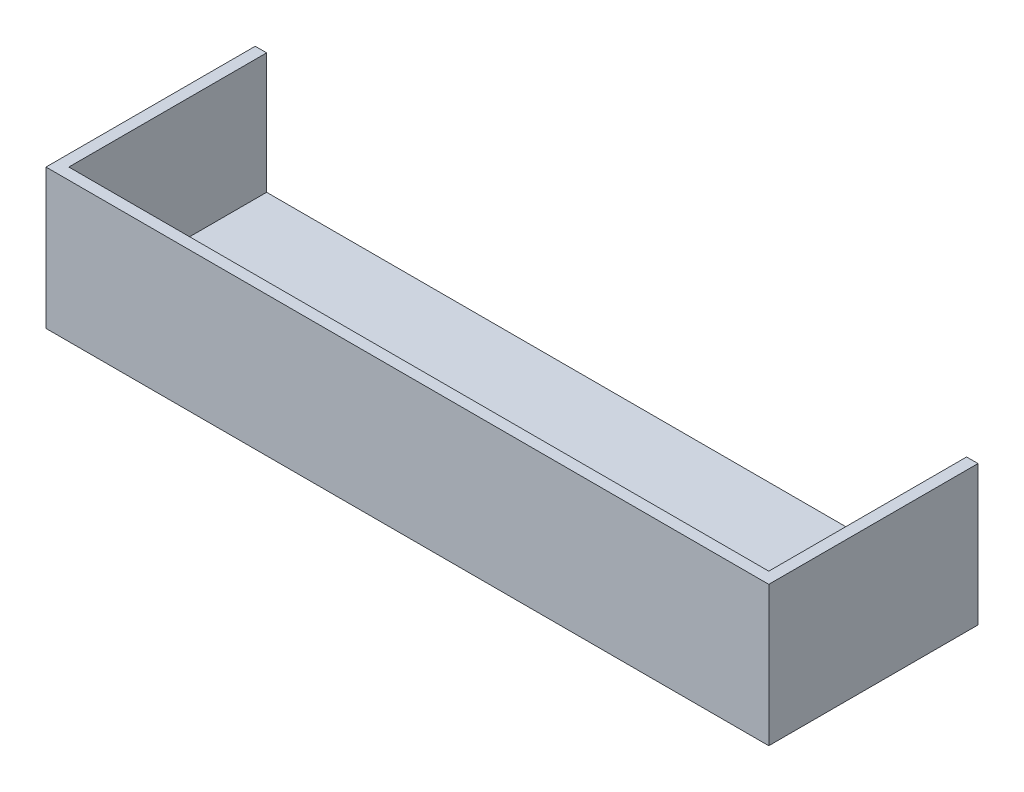
SolidWorks part; units mm, degrees
ref_plane "Front Plane" through (0, 0, 0) normal (0, 0, 1) x (1, 0, 0)
ref_plane "Top Plane" through (0, 0, 0) normal (0, 1, 0) x (1, 0, 0)
ref_plane "Right Plane" through (0, 0, 0) normal (1, 0, 0) x (0, 0, -1)
sketch "Sketch1" plane through (0, 0, 0) normal (0, 1, 0) x (1, 0, 0)
  line L0 (0, 55) -> (3, 55.0013)
  line L1 (0, 0) -> (190, 0)
  line L2 (0, 0) -> (0, 55)
  line L4 (190, 0) -> (190, 55)
  line L6 (3, 55.0013) -> (3, 3)
  line L7 (3, 3) -> (187, 3)
  line L8 (187, 55.0013) -> (187, 3)
  line L9 (187, 55.0013) -> (190, 55)
  dimension "D1" = 190
  dimension "D2" = 55
  dimension "D3" = 3
  dimension "D4" = 3
  dimension "D5" = 3
extrude "Boss-Extrude1" add sketch "Sketch1" along normal blind 31.75
sketch "Sketch2" plane through (0, 0, 0) normal (0, -1, 0) x (1, 0, 0)
  line L1 (0, 0) -> (190, 0)
  line L2 (0, 0) -> (0, -55)
  line L3 (0, -55) -> (190, -55)
  line L4 (190, 0) -> (190, -55)
extrude "Boss-Extrude2" add sketch "Sketch2" along normal blind 5
